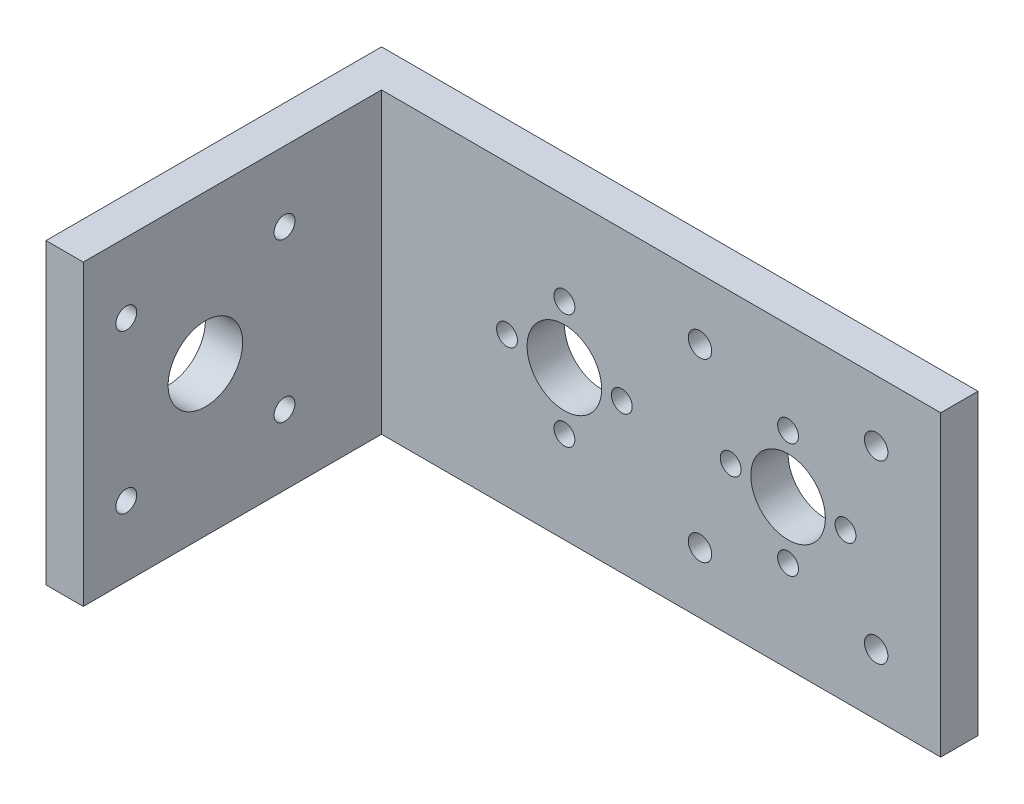
SolidWorks part; units mm, degrees
material "Copper"
ref_plane "Front Plane" through (0, 0, 0) normal (0, 0, 1) x (1, 0, 0)
ref_plane "Top Plane" through (0, 0, 0) normal (0, 1, 0) x (1, 0, 0)
ref_plane "Right Plane" through (0, 0, 0) normal (1, 0, 0) x (0, 0, -1)
sketch "Sketch1" plane through (0, 0, 0) normal (0, 0, 1) x (1, 0, 0)
  line L1 (0, 0) -> (-101.6, 0)
  line L2 (0, 0) -> (0, -50.8)
  line L3 (0, -50.8) -> (-101.6, -50.8)
  line L4 (-101.6, 0) -> (-101.6, -50.8)
  dimension "D1" = 50.8
  dimension "D2" = 101.6
extrude "Boss-Extrude1" add sketch "Sketch1" along normal blind 6.35
sketch "Sketch2" plane through (0, 0, 6.35) normal (0, 0, 1) x (1, 0, 0)
  line L0 (0, -25.4) -> (-101.6, -25.4) construction
  line L3 (0, -50.8) -> (0, 0) construction
  line L4 (-101.6, 0) -> (-101.6, -50.8) construction
  circle A0 centre (-11, -10.4) radius 2
  circle A1 centre (-41, -10.4) radius 2
  circle A2 centre (-41, -40.4) radius 2
  circle A3 centre (-11, -40.4) radius 2
  dimension "D1" = 15
  dimension "D7" = 4
  dimension "D8" = 4
  dimension "D9" = 4
  dimension "D10" = 4
  dimension "D2" = 15
  dimension "D3" = 15
  dimension "D4" = 15
  dimension "D5" = 30
  dimension "D6" = 30
  dimension "D11" = 11
  dimension "D12" = 11
extrude "Cut-Extrude1" cut sketch "Sketch2" against normal blind 6.35
sketch "Sketch3" plane through (0, 0, 6.35) normal (0, 0, 1) x (1, 0, 0)
  line L0 (0, -25.4) -> (-101.6, -25.4) construction
  line L1 (0, -50.8) -> (0, 0) construction
  line L2 (-101.6, 0) -> (-101.6, -50.8) construction
  circle A0 centre (-26, -15.621) radius 1.778
  dimension "D1" = 26
  dimension "D3" = 3.556
  dimension "D2" = 9.779
extrude "Cut-Extrude2" cut sketch "Sketch3" against normal blind 6.35
sketch "Sketch4" plane through (0, 0, 6.35) normal (0, 0, 1) x (1, 0, 0)
  line L0 (0, -25.4) -> (-101.6, -25.4) construction
  line L3 (0, -50.8) -> (0, 0) construction
  line L4 (-101.6, 0) -> (-101.6, -50.8) construction
  circle A0 centre (-26, -25.4) radius 6.35
  dimension "D1" = 12.7
  dimension "D2" = 26
extrude "Cut-Extrude3" cut sketch "Sketch4" against normal blind 6.35
pattern_circular "CirPattern1" count 4 over 360 about axis through (-26, -25.4, 6.35) along (0, 0, 1) of "Cut-Extrude2"
sketch "Sketch5" plane through (0, 0, 6.35) normal (0, 0, 1) x (1, 0, 0)
  line L0 (-101.6, -50.8) -> (0, -50.8) construction
  line L1 (-101.6, 0) -> (-95.25, 0)
  line L2 (-101.6, 0) -> (-101.6, -50.8)
  line L3 (-101.6, -50.8) -> (-95.25, -50.8)
  line L4 (-95.25, 0) -> (-95.25, -50.8)
  dimension "D1" = 6.35
extrude "Boss-Extrude2" add sketch "Sketch5" along normal blind 50.8
sketch "Sketch6" plane through (-95.25, 0, 0) normal (1, 0, 0) x (0, 0, -1)
  line L0 (-6.35, -50.8) -> (-6.35, 0) construction
  line L1 (-57.15, -50.8) -> (-6.35, -50.8) construction
  circle A0 centre (-36.35, -25.4) radius 6.35
  dimension "D1" = 30
  dimension "D2" = 12.7
  dimension "D3" = 25.4
extrude "Cut-Extrude4" cut sketch "Sketch6" against normal blind 6.35
sketch "Sketch7" plane through (-95.25, 0, 0) normal (1, 0, 0) x (0, 0, -1)
  circle A0 centre (-49.8247, -11.9253) radius 1.778
  circle A1 centre (-36.35, -25.4) radius 6.35 construction
  point P6 (-49.3608, -11.8802)
  dimension "D1" = 3.556
  dimension "D2" = 13.4747
  dimension "D3" = 13.4747
extrude "Cut-Extrude5" cut sketch "Sketch7" against normal blind 6.35
pattern_circular "CirPattern2" count 4 over 360 about axis through (-95.25, -25.4, 36.35) along (1, 0, 0) of "Cut-Extrude5"
pattern_linear "LPattern1" count 2 spacing 38.1 along (-1, 0, 0) of "CirPattern1", "Cut-Extrude3"
